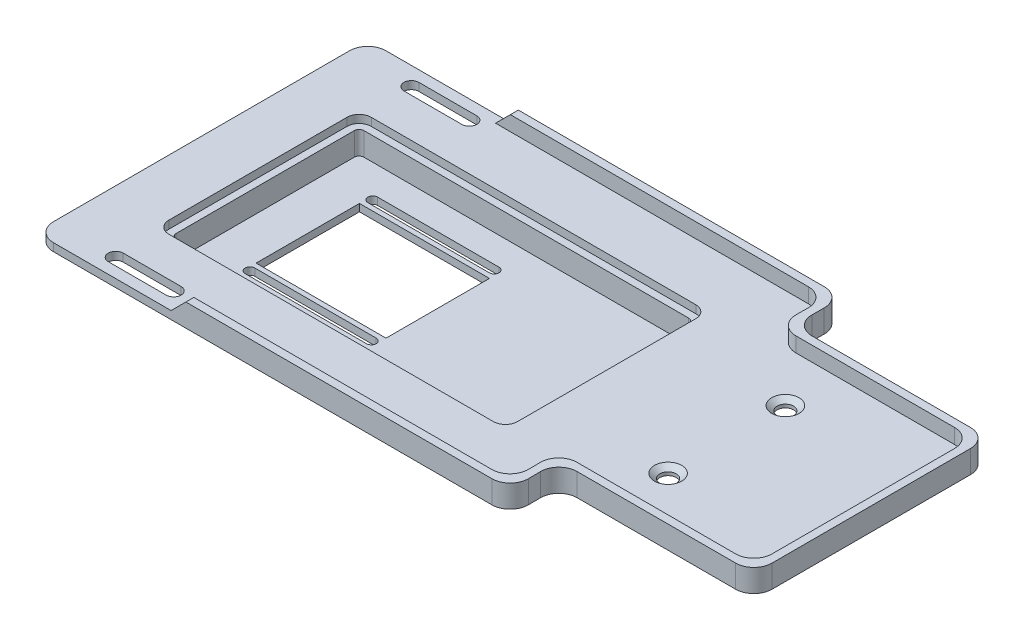
SolidWorks part; units mm, degrees
ref_plane "Front Plane" through (0, 0, 0) normal (0, 0, 1) x (1, 0, 0)
ref_plane "Top Plane" through (0, 0, 0) normal (0, 1, 0) x (1, 0, 0)
ref_plane "Right Plane" through (0, 0, 0) normal (1, 0, 0) x (0, 0, -1)
sketch "Sketch3" plane through (0, 0, 0) normal (0, 1, 0) x (1, 0, 0)
  line L0 (87.5652, 62.0125) -> (87.54, 59.4982)
  line L1 (-8.0055, -3.7155) -> (83.7554, -3.7155)
  line L2 (-11.8155, 0.0945) -> (-11.8155, 62.0506)
  line L3 (-8.0055, 65.8606) -> (83.7554, 65.8606)
  line L5 (91.3499, 55.6501) -> (124.5444, 55.6501)
  line L7 (91.3499, 6.4949) -> (124.5444, 6.4949)
  line L8 (128.3544, 51.8401) -> (128.3544, 10.3049)
  line L9 (87.5652, 0.1326) -> (87.54, 2.6468)
  line L10 (14.7783, 64.1969) -> (82.075, 64.1969)
  line L11 (85.8848, 60.3488) -> (85.8596, 57.8345)
  line L12 (89.6694, 53.9864) -> (122.8807, 53.9864)
  line L13 (126.6907, 50.1764) -> (126.6907, 11.9686)
  line L14 (89.6694, 8.1586) -> (122.8807, 8.1586)
  line L15 (85.8848, 1.7963) -> (85.8596, 4.3105)
  line L16 (14.7783, -2.0518) -> (82.075, -2.0518)
  line L18 (14.7783, -2.0518) -> (14.7783, -3.7155)
  line L19 (14.7783, 65.8606) -> (14.7783, 64.1969)
  line L20 (-10.1518, -2.0518) -> (85.9232, -2.0518) construction
  line L21 (-10.1518, -2.0518) -> (-10.1518, 64.1969) construction
  line L22 (-10.1518, 64.1969) -> (85.9232, 64.1969) construction
  line L23 (85.8211, 53.9864) -> (126.6907, 53.9864) construction
  line L24 (2.5228, 52.2589) -> (70.4424, 52.2589)
  line L25 (-0.0172, 49.7189) -> (-0.0172, 12.4262)
  line L26 (2.5228, 9.8862) -> (70.4424, 9.8862)
  line L27 (72.9824, 49.7189) -> (72.9824, 12.4262)
  line L28 (85.9232, 64.1969) -> (85.8211, 53.9864) construction
  line L29 (87.6037, 65.8606) -> (87.5016, 55.6501) construction
  line L30 (87.5016, 55.6501) -> (128.3544, 55.6501) construction
  line L31 (-11.8155, 65.8606) -> (87.6037, 65.8606) construction
  line L32 (87.6037, -3.7155) -> (87.5016, 6.4949) construction
  line L33 (-11.8155, -3.7155) -> (87.6037, -3.7155) construction
  line L34 (85.9232, -2.0518) -> (85.8211, 8.1586) construction
  line L35 (87.5016, 6.4949) -> (128.3544, 6.4949) construction
  line L36 (85.8211, 8.1586) -> (126.6907, 8.1586) construction
  line L37 (128.3544, 55.6501) -> (128.3544, 6.4949) construction
  line L38 (126.6907, 53.9864) -> (126.6907, 8.1586) construction
  line L39 (-11.8155, -3.7155) -> (-11.8155, 65.8606) construction
  line L40 (1.1766, 62.0125) -> (13.2924, 62.0125) construction
  line L41 (1.1766, 63.5746) -> (13.2924, 63.5746)
  line L42 (1.1766, 60.4504) -> (13.2924, 60.4504)
  line L43 (1.1766, 0.1326) -> (13.2924, 0.1326) construction
  line L44 (1.1766, 1.6947) -> (13.2924, 1.6947)
  line L45 (1.1766, -1.4295) -> (13.2924, -1.4295)
  line L46 (98.103, 43.3471) -> (98.103, 18.798) construction
  arc A0 (89.6694, 53.9864) -> (85.8596, 57.8345) centre (89.6694, 57.7964) cw
  arc A1 (87.54, 59.4982) -> (91.3499, 55.6501) centre (91.3499, 59.4601) ccw
  arc A2 (87.5652, 62.0125) -> (83.7554, 65.8606) centre (83.7554, 62.0506) ccw
  arc A3 (82.075, 64.1969) -> (85.8848, 60.3488) centre (82.075, 60.3869) cw
  arc A4 (87.5652, 0.1326) -> (83.7554, -3.7155) centre (83.7554, 0.0945) cw
  arc A5 (82.075, -2.0518) -> (85.8848, 1.7963) centre (82.075, 1.7582) ccw
  arc A6 (91.3499, 6.4949) -> (87.54, 2.6468) centre (91.3499, 2.6849) ccw
  arc A7 (89.6694, 8.1586) -> (85.8596, 4.3105) centre (89.6694, 4.3486) ccw
  arc A8 (128.3544, 51.8401) -> (124.5444, 55.6501) centre (124.5444, 51.8401) ccw
  arc A9 (122.8807, 53.9864) -> (126.6907, 50.1764) centre (122.8807, 50.1764) cw
  arc A10 (122.8807, 8.1586) -> (126.6907, 11.9686) centre (122.8807, 11.9686) ccw
  arc A11 (128.3544, 10.3049) -> (124.5444, 6.4949) centre (124.5444, 10.3049) cw
  arc A12 (-8.0055, -3.7155) -> (-11.8155, 0.0945) centre (-8.0055, 0.0945) cw
  arc A13 (-11.8155, 62.0506) -> (-8.0055, 65.8606) centre (-8.0055, 62.0506) cw
  arc A14 (70.4424, 52.2589) -> (72.9824, 49.7189) centre (70.4424, 49.7189) cw
  arc A15 (70.4424, 9.8862) -> (72.9824, 12.4262) centre (70.4424, 12.4262) ccw
  arc A16 (2.5228, 9.8862) -> (-0.0172, 12.4262) centre (2.5228, 12.4262) cw
  arc A17 (-0.0172, 49.7189) -> (2.5228, 52.2589) centre (2.5228, 49.7189) cw
  arc A18 (1.1766, 63.5746) -> (1.1766, 60.4504) centre (1.1766, 62.0125) ccw
  arc A19 (13.2924, 60.4504) -> (13.2924, 63.5746) centre (13.2924, 62.0125) ccw
  arc A20 (1.1766, 1.6947) -> (1.1766, -1.4295) centre (1.1766, 0.1326) ccw
  arc A21 (13.2924, -1.4295) -> (13.2924, 1.6947) centre (13.2924, 0.1326) ccw
  circle A22 centre (98.103, 43.3471) radius 1.7208
  circle A23 centre (98.103, 18.798) radius 1.7208
  point P4 (98.103, 31.0725)
  point P9 (128.3544, 31.0725)
  point P10 (-11.8155, 31.0725)
  point P33 (87.5016, 55.6501)
  point P43 (87.6037, -3.7155)
  point P81 (7.2345, 62.0125)
  point P86 (-0.3855, 62.0125)
  point P87 (14.8545, 62.0125)
  point P90 (7.2345, 0.1326)
  point P95 (-0.3855, 0.1326)
  point P96 (14.8545, 0.1326)
  point P101 (126.6907, 31.0725)
  point P102 (0, 0)
  point P103 (98.103, 18.798)
  point P104 (98.103, 43.3471)
  dimension "D14" = 3.81
  dimension "D2" = 2.54
  dimension "D20" = 3.4417
  dimension "D21" = 3.4417
  dimension "D3" = 140.1699
  dimension "D4" = 2.286
  dimension "D5" = 3.1242
  dimension "D6" = 11.43
  dimension "D8" = 26.5938
  dimension "D9" = 26.5938
  dimension "D10" = 13.6017
  dimension "D11" = 13.6017
  dimension "D12" = 11.7983
  dimension "D13" = 55.372
  dimension "D15" = 15.24
  dimension "D16" = 2.286
  dimension "D17" = 3.1242
  dimension "D18" = 15.24
  dimension "D19" = 11.43
  dimension "D22" = 30.2514
  dimension "D23" = 24.5491
  dimension "D7" = 1.6637
extrude "Boss-Extrude3" add sketch "Sketch3" along normal blind 1.651 contours A13 L2 A12 L1 L18 L16 A5 L15 A7 L14 A10 L13 A9 L12 A0 L11 A3 L10 L19 L3 A23 A22 A21 L45 A20 L44 A19 L42 A18 L41 L25 A17 L24 A14 L27 A15 L26 A16 region at (13.2283, 0, -65.0288)
extrude "Boss-Extrude4" add sketch "Sketch3<4>" along normal blind 4.7498 contours A11 L8 A8 L5 A1 L0 A2 L3 L19 L10 A3 L11 A0 L12 A9 L13 A10 L14 A7 L15 A5 L16 L18 L1 A4 L9 A6 L7 region at (86.2208, 0, -60.7687)
sketch "Sketch3<4>" plane through (0, 0, 0) normal (0, 1, 0) x (1, 0, 0) same geometry as "Sketch3"
extrude "Boss-Extrude5" add sketch "Sketch3<5>" against normal blind 6.35 separate body contours A17 L25 A16 L26 A15 L27 A14 L24 region at (36.4826, 0, -31.0725)
sketch "Sketch3<5>" plane through (0, 0, 0) normal (0, 1, 0) x (1, 0, 0) same geometry as "Sketch3"
shell "Shell1" thickness 1.524 removed face at (36.4826, 0, -31.0725)
sketch "Sketch6" plane through (0, -4.826, 0) normal (0, 1, 0) x (1, 0, 0)
  line L0 (11.1817, 43.9249) -> (36.5817, 43.9249) construction
  line L1 (11.1817, 44.9409) -> (36.5817, 44.9409)
  line L2 (11.1817, 42.9089) -> (36.5817, 42.9089)
  line L3 (11.1817, 18.2201) -> (36.5817, 18.2201) construction
  line L4 (11.1817, 19.2361) -> (36.5817, 19.2361)
  line L5 (11.1817, 17.2041) -> (36.5817, 17.2041)
  line L6 (23.8817, 43.9249) -> (23.8817, 18.2201) construction
  line L7 (8.6417, 50.7349) -> (8.6417, 11.4102) construction
  line L8 (2.5228, 50.7349) -> (70.4424, 50.7349) construction
  line L9 (2.5228, 11.4102) -> (70.4424, 11.4102) construction
  line L11 (10.4197, 41.8929) -> (37.6175, 41.8929)
  line L12 (10.4197, 41.8929) -> (10.4197, 20.2521)
  line L13 (10.4197, 20.2521) -> (37.6175, 20.2521)
  line L14 (37.6175, 41.8929) -> (37.6175, 20.2521)
  arc A0 (11.1817, 44.9409) -> (11.1817, 42.9089) centre (11.1817, 43.9249) ccw
  arc A1 (36.5817, 42.9089) -> (36.5817, 44.9409) centre (36.5817, 43.9249) ccw
  arc A2 (11.1817, 19.2361) -> (11.1817, 17.2041) centre (11.1817, 18.2201) ccw
  arc A3 (36.5817, 17.2041) -> (36.5817, 19.2361) centre (36.5817, 18.2201) ccw
  point P2 (23.8817, 43.9249)
  point P9 (23.8817, 18.2201)
  point P22 (23.8817, 31.0725)
  point P23 (8.6417, 31.0725)
  point P28 (10.1657, 43.9249)
  dimension "D1" = 25.7048
  dimension "D2" = 2.032
  dimension "D3" = 2.032
  dimension "D4" = 25.4
  dimension "D5" = 25.4
  dimension "D6" = 15.24
  dimension "D7" = 1.016
  dimension "D8" = 1.016
  dimension "D9" = 0.254
extrude "Cut-Extrude1" cut sketch "Sketch6" against normal blind 6.35
sketch "Sketch7" plane through (0, 1.651, 0) normal (0, 1, 0) x (1, 0, 0)
  point P0 (98.103, 43.3471)
  point P1 (98.103, 18.798)
hole_wizard "CSK for #4 Flat Head Machine Screw (100)1" positions "Sketch8" profile "Sketch9" countersink size "#4" standard "ANSI Inch" end condition through all
sketch "Sketch8" plane through (0, 1.651, 0) normal (0, 1, 0) x (1, 0, 0)
  point P0 (98.103, 43.3471)
  point P3 (98.103, 18.798)
sketch "Sketch9" plane through (98.103, 1.651, -43.3471) normal (1, 0, 0) x (0, 0, 1)
  line L0 (0, 0) -> (0, 8.001)
  line L1 (0, 8.001) -> (1.6319, 8.001)
  line L2 (1.6319, 8.001) -> (1.6319, 1.0284)
  line L3 (1.6319, 1.0284) -> (2.8575, 0)
  line L5 (2.8575, 0) -> (0, 0)
  line L6 (-1.6319, 1.0284) -> (-2.8575, 0) construction
  line L11 (0, -6.35) -> (0, 107.95) construction
  dimension "Thru Hole Dia." = 3.2639
  dimension "Thru Hole Depth" = 8.001
  dimension "Near C'Sink Dia." = 5.715
  dimension "Near C'Sink Angle" = 100
chamfer "Chamfer2" distance 4.92 2 edges at (14.7783, 4.7498, 2.8837) (14.7783, 4.7498, -65.0288)
